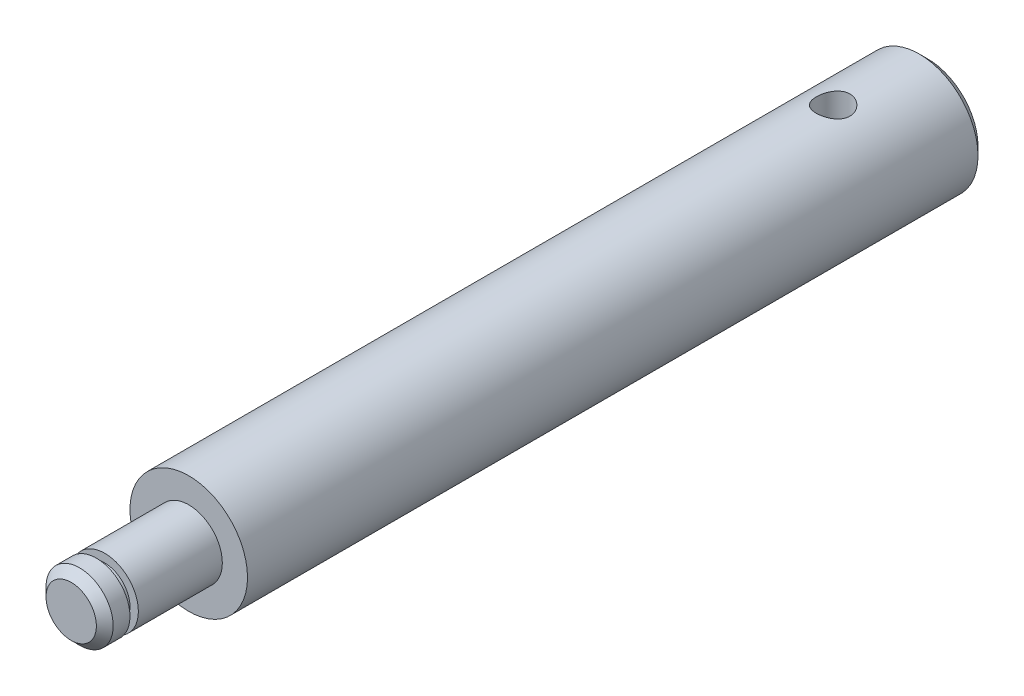
SolidWorks part; units mm, degrees
material "Alliage de zinc AC41A, brut"
ref_plane "Plan de face" through (0, 0, 0) normal (0, 0, 1) x (1, 0, 0)
ref_plane "Plan de dessus" through (0, 0, 0) normal (0, 1, 0) x (1, 0, 0)
ref_plane "Plan de droite" through (0, 0, 0) normal (1, 0, 0) x (0, 0, -1)
sketch "Esquisse1" plane through (0, 0, 0) normal (0, 0, 1) x (1, 0, 0)
  circle A0 centre (0, 0) radius 3.5
  dimension "D1" = 7
extrude "Boss.-Extru.1" add sketch "Esquisse1" along normal blind 44
sketch "Esquisse2" plane through (0, 0, 44) normal (0, 0, 1) x (1, 0, 0)
  circle A0 centre (0, 0) radius 2
  dimension "D1" = 4
extrude "Boss.-Extru.2" add sketch "Esquisse2" along normal blind 5
sketch "Esquisse3" plane through (0, 0, 49) normal (0, 0, 1) x (1, 0, 0)
  circle A0 centre (0, 0) radius 1.5
  dimension "D1" = 3
extrude "Boss.-Extru.3" add sketch "Esquisse3" along normal blind 0.5
sketch "Esquisse4" plane through (0, 0, 49.5) normal (0, 0, 1) x (1, 0, 0)
  circle A0 centre (0, 0) radius 2
  dimension "D1" = 4
extrude "Boss.-Extru.4" add sketch "Esquisse4" along normal blind 1.5
chamfer "Chanfrein1" distance 0.5 angle 45 1 edges at (2, 0, 51)
chamfer "Chanfrein2" distance 0.5 angle 45 1 edges at (3.5, 0, 0)
hole_wizard "Diamètre du perçage Ø2.0 (2)3" positions "Esquisse3D1" profile "Esquisse12" hole size "Ø2.0" standard "ISO" end condition through all
sketch3d "Esquisse3D1"
  line L0 (0, 0, 0) -> (0, 0, 5.625) construction
  line L2 (0, 3.5, 5.625) -> (0, 0, 5.625) construction
  point P0 (0, 3.5, 5.625)
  dimension "D1" = 5.625
sketch "Esquisse12" plane through (0, 3.5, 5.625) normal (1, 0, 0) x (0, 0, 1)
  line L0 (0, 0) -> (0, 7)
  line L1 (0, 7) -> (1, 7)
  line L2 (1, 7) -> (1, 0)
  line L5 (1, 0) -> (0, 0)
  line L11 (0, -6.35) -> (0, 107.95) construction
  dimension "Diamètre du perçage jusqu'au prochain" = 2
  dimension "Profondeur du perçage jusqu'au prochain" = 7
cosmetic thread "Représentation de filetage1" parameters "D2"=3
